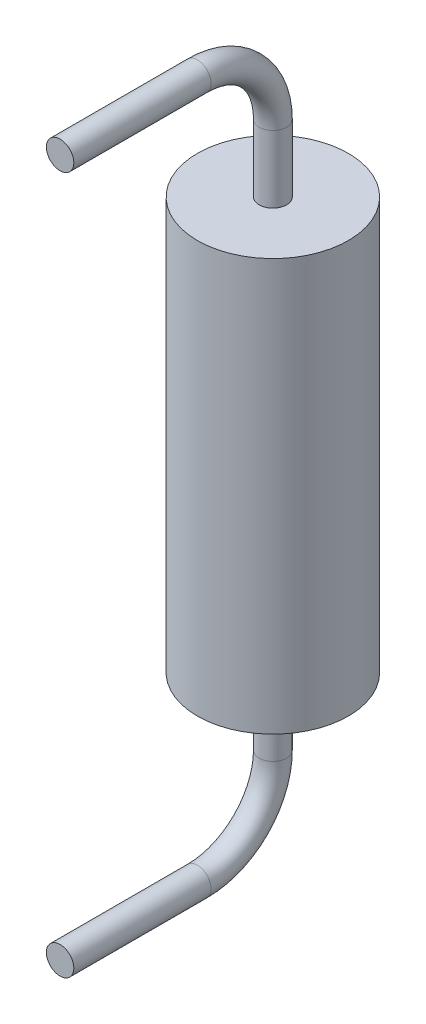
SolidWorks part; units mm, degrees
ref_plane "Front Plane" through (0, 0, 0) normal (0, 0, 1) x (1, 0, 0)
ref_plane "Top Plane" through (0, 0, 0) normal (0, 1, 0) x (1, 0, 0)
ref_plane "Right Plane" through (0, 0, 0) normal (1, 0, 0) x (0, 0, -1)
sketch "Sketch2" plane through (0, 0, 0) normal (0, 1, 0) x (1, 0, 0)
  circle A0 centre (0, 0) radius 1.1
  dimension "D1" = 2.2
extrude "Boss-Extrude1" add sketch "Sketch2" along normal blind 3 and the other way blind 3
sketch "Sketch3" plane through (0, 0, 0) normal (1, 0, 0) x (0, 0, -1)
  line L0 (0, 3) -> (0, 3.98)
  line L1 (1.1, 3) -> (-1.1, 3) construction
  line L2 (-1.1, 5.08) -> (-3.1, 5.08)
  arc A0 (0, 3.98) -> (-1.1, 5.08) centre (-1.1, 3.98) ccw
  dimension "D1" = 2.08
  dimension "D2" = 2
sweep "Sweep1" add path "Sketch3" circular profile diameter 0.4 parameters "D3"=0.4
mirror "Mirror1" about plane through (0, 0, 0) normal (0, 1, 0) of "Sweep1"
